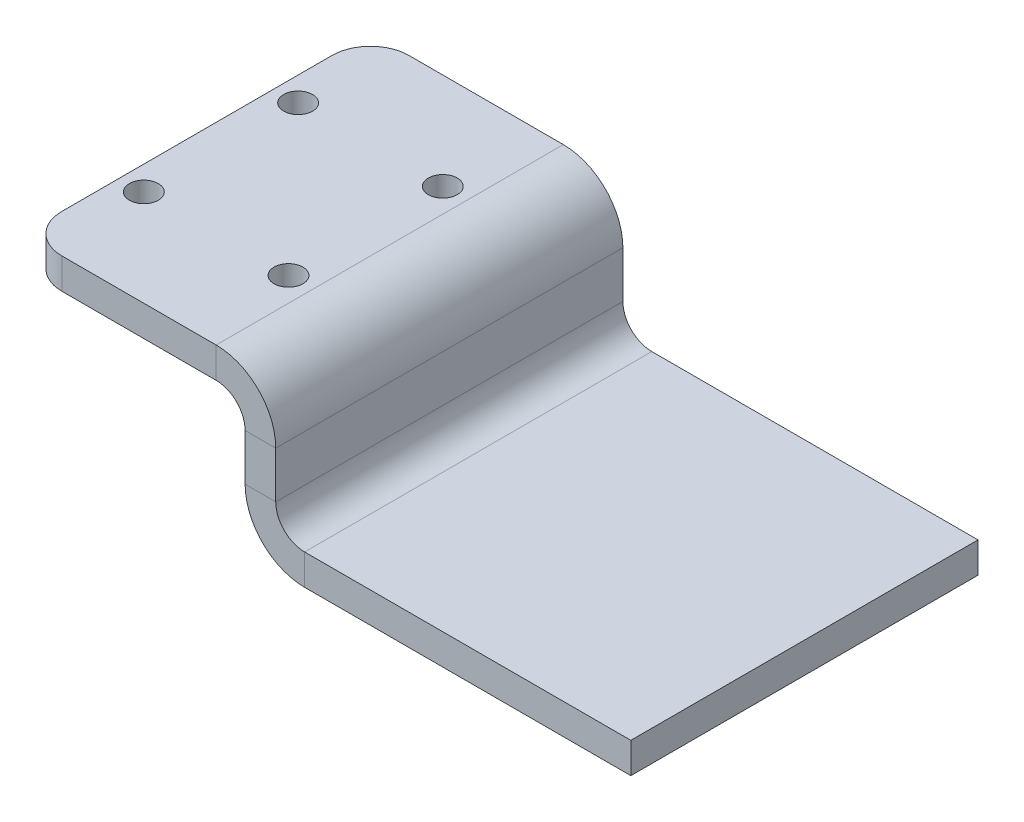
SolidWorks part; units mm, degrees
note: The reader was unsure of these and kept them because the rebuilt part matched: flange length of "Edge-Flange4", "Edge-Flange5".
ref_plane "Front Plane" through (0, 0, 0) normal (0, 0, 1) x (1, 0, 0)
ref_plane "Top Plane" through (0, 0, 0) normal (0, 1, 0) x (1, 0, 0)
ref_plane "Right Plane" through (0, 0, 0) normal (1, 0, 0) x (0, 0, -1)
sketch "Sketch2" plane through (0, 0, 0) normal (0, 1, 0) x (1, 0, 0)
  line L0 (23, -18) -> (0, -18)
  line L1 (23, -18) -> (23, 18)
  line L2 (0, -18) -> (0, 18)
  line L3 (23, 18) -> (0, 18)
  line L4 (23, -18) -> (0, 18) construction
  line L5 (0, -18) -> (23, 18) construction
  line L6 (23, 0) -> (0, 0) construction
  line L8 (2.5, -8) -> (17.5, -8) construction
  line L9 (2.5, -8) -> (2.5, 8) construction
  line L10 (2.5, 8) -> (17.5, 8) construction
  line L11 (17.5, -8) -> (17.5, 8) construction
  line L12 (2.5, -8) -> (17.5, 8) construction
  line L13 (2.5, 8) -> (17.5, -8) construction
  circle A0 centre (2.5, 8) radius 1.5 construction
  circle A1 centre (17.5, 8) radius 1.5 construction
  circle A2 centre (2.5, -8) radius 1.5 construction
  circle A3 centre (17.5, -8) radius 1.5 construction
  point P1 (11.5, 0)
  point P10 (0, 0)
  point P13 (10, 0)
  dimension "D3" = 3
  dimension "D4" = 2.5
  dimension "D1" = 36
  dimension "D2" = 23
  dimension "D5" = 15
  dimension "D6" = 16
base flange "Base-Flange1" sketch "Sketch2" thickness 3.175 reverse thickness direction no parameters "D1"=3
edge flange "Edge-Flange4" sketch "Sketch16" flange angle 90 flange length 14 flange position material outside bend radius 3 thickness 3.175 relief rectangular parameters "D6"=10
sketch "Sketch16" plane through (23, -3.175, 0) normal (1, 0, 0) x (0, 0, 1)
  line L0 (18, 0) -> (-18, 0) construction
  line L1 (18, 0) -> (-18, 0)
  line L2 (-18, 0) -> (-18, 10.825)
  line L3 (-18, 10.825) -> (18, 10.825)
  line L4 (18, 10.825) -> (18, 0)
bend "EdgeBend4" bend radius 3 bend angle 90 parameters "D5"=1
edge flange "Edge-Flange5" sketch "Sketch19" flange angle 90 flange length 40 flange position material outside bend radius 3 thickness 3.175 relief rectangular parameters "D6"=10
sketch "Sketch19" plane through (26.175, -14, 0) normal (0, -1, 0) x (0, 0, -1)
  line L2 (-18, 0) -> (-18, 36.825)
  line L3 (-18, 36.825) -> (18, 36.825)
  line L4 (18, 36.825) -> (18, 0)
  line L5 (-18, 0) -> (18, 0) construction
  line L6 (-18, 0) -> (18, 0)
bend "EdgeBend5" bend radius 3 bend angle 90 parameters "D5"=2
sketch "Sketch20" plane through (0, 0, 0) normal (0, 1, 0) x (1, 0, 0)
  circle A0 centre (17.5, -8) radius 1.5 construction
  circle A1 centre (17.5, 8) radius 1.5 construction
  circle A2 centre (2.5, 8) radius 1.5 construction
  circle A3 centre (2.5, -8) radius 1.5 construction
  circle A4 centre (17.5, -8) radius 1.5
  circle A5 centre (17.5, 8) radius 1.5
  circle A6 centre (2.5, 8) radius 1.5
  circle A7 centre (2.5, -8) radius 1.5
extrude "Cut-Extrude1" cut sketch "Sketch20" against normal through all normal cut yes
fillet "Fillet1" radius 4 2 edges at (0, -1.5875, 18) (0, -1.5875, -18)
sketch "Bend-Lines1" [suppressed] plane through (0, 0, 0) normal (0, 1, 0) x (1, 0, 0)
sketch "Bounding-Box1" [suppressed] plane through (0, 0, 0) normal (0, 1, 0) x (1, 0, 0)
sheet metal parameters "Sheet-Metal2" thickness 3.175 parameters "D1"=3
flat pattern "Flat-Pattern2" [suppressed]
sketch "Bend-Lines2" plane through (0, 0, 0) normal (0, 1, 0) x (1, 0, 0)
sketch3d "Bounding-Box2" [suppressed]
  line L0 (0, 18, 0) -> (0, -18, 0) construction
  line L1 (22, 18, 0) -> (22, -18, 0) construction
  line L2 (0, 18, 0) -> (22, 18, 0) construction
  line L3 (0, -18, 0) -> (22, -18, 0) construction
sheet metal parameters "Sheet-Metal3" thickness 3.175 parameters "D1"=3
flat pattern "Flat-Pattern2"
sketch "Bend-Lines2" plane through (0, 0, 0) normal (0, 1, 0) x (1, 0, 0)
  line L0 (22.603, -18) -> (22.603, 18) construction
  line L1 (22.603, -18) -> (22.603, 18) construction
sketch3d "Bounding-Box2" [suppressed]
  line L0 (0, 18, 0) -> (0, -18, 0) construction
  line L1 (30.031, 18, 0) -> (30.031, -18, 0) construction
  line L2 (0, 18, 0) -> (30.031, 18, 0) construction
  line L3 (0, -18, 0) -> (30.031, -18, 0) construction
bend of the flat pattern "Flatten-<EdgeBend4>1"
sheet metal parameters "Sheet-Metal4" thickness 3.175 parameters "D1"=3
flat pattern "Flat-Pattern2"
sketch "Bend-Lines2" plane through (0, 0, 0) normal (0, 1, 0) x (1, 0, 0)
  line L0 (22.603, -18) -> (22.603, 18) construction
  line L1 (22.603, -18) -> (22.603, 18) construction
  line L2 (30.634, -18) -> (30.634, 18) construction
  line L3 (30.634, -18) -> (30.634, 18) construction
sketch3d "Bounding-Box2" [suppressed]
  line L0 (68.0621, -18, 0) -> (0, -18, 0) construction
  line L1 (68.0621, 18, 0) -> (0, 18, 0) construction
  line L2 (68.0621, -18, 0) -> (68.0621, 18, 0) construction
  line L3 (0, -18, 0) -> (0, 18, 0) construction
bend of the flat pattern "Flatten-<EdgeBend4>1"
bend of the flat pattern "Flatten-<EdgeBend5>1"
sheet metal parameters "Sheet-Metal5" thickness 3.175 parameters "D1"=3
flat pattern "Flat-Pattern2"
sketch "Bend-Lines2" plane through (0, 0, 0) normal (0, 1, 0) x (1, 0, 0)
  line L0 (23.603, -18) -> (23.603, 18) construction
  line L1 (23.603, -18) -> (23.603, 18) construction
  line L2 (35.634, -18) -> (35.634, 18) construction
  line L3 (35.634, -18) -> (35.634, 18) construction
sketch3d "Bounding-Box2" [suppressed]
  line L0 (0, -18, 0) -> (73.0621, -18, 0) construction
  line L1 (0, 18, 0) -> (73.0621, 18, 0) construction
  line L2 (0, -18, 0) -> (0, 18, 0) construction
  line L3 (73.0621, -18, 0) -> (73.0621, 18, 0) construction
bend of the flat pattern "Flatten-<EdgeBend4>1"
bend of the flat pattern "Flatten-<EdgeBend5>1"
